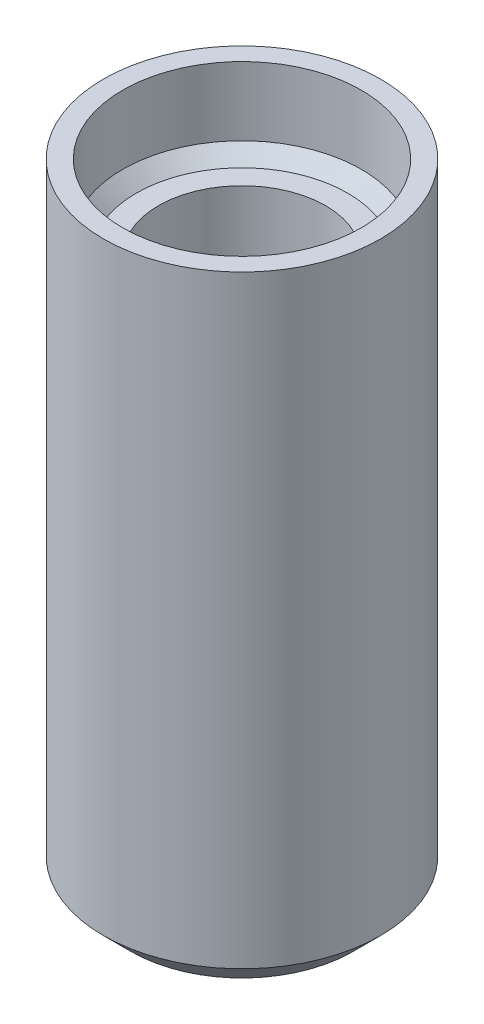
SolidWorks part; units mm, degrees
ref_plane "Front Plane" through (0, 0, 0) normal (0, 0, 1) x (1, 0, 0)
ref_plane "Top Plane" through (0, 0, 0) normal (0, 1, 0) x (1, 0, 0)
ref_plane "Right Plane" through (0, 0, 0) normal (1, 0, 0) x (0, 0, -1)
sketch "Sketch1" plane through (0, 0, 0) normal (0, 1, 0) x (1, 0, 0)
  line L0 (-2.5652, -1.65) -> (2.5652, -1.65)
  circle A0 centre (0, 0) radius 3.05
  circle A1 centre (0, 0) radius 5.05
  dimension "D1" = 6.1
  dimension "D3" = 1.65
  dimension "D2" = 2
extrude "Boss-Extrude1" add sketch "Sketch1" along normal blind 20 contours A1 A0 | L0 A0 region at (0, 0, 2.2227) region at (-4.9072, 0, 0)
sketch "Sketch2" plane through (0, 0, 0) normal (0, -1, 0) x (1, 0, 0)
  circle A1 centre (0, 0) radius 5.05
  circle A2 centre (0, 0) radius 5.05
  dimension "D1" = 0
extrude "Boss-Extrude2" add sketch "Sketch2" against normal blind 2
sketch "Sketch4" plane through (0, 20, 0) normal (0, 1, 0) x (1, 0, 0)
  circle A0 centre (0, 0) radius 4.35
  circle A1 centre (0, 0) radius 5.05
  circle A2 centre (0, 0) radius 5.05
  dimension "D1" = 0
  dimension "D2" = 0.7
extrude "Boss-Extrude3" add sketch "Sketch4" along normal blind 3
chamfer "Chamfer1" distance 1 angle 45 1 edges at (0, 0, 5.05)
chamfer "Chamfer2" distance 0.5 angle 45 1 edges at (0, 20, 4.35)
sketch "Sketch5" plane through (0, 0, 0) normal (0, -1, 0) x (1, 0, 0)
  line L0 (-1.326, 0) -> (1.326, 0) construction
  line L1 (-3.5217, -2) -> (3.5217, -2) construction
  circle A0 centre (0, 0) radius 4.05 construction
  text T0 "<b>1</b>" font "Calibri" height in points 16
  dimension "D1" = 2
extrude "Cut-Extrude1" cut sketch "Sketch5" against normal blind 0.4
extrude "Boss-Extrude4" add sketch "Sketch5<2>" against normal blind 0.4 separate body
sketch "Sketch5<2>" plane through (0, 0, 0) normal (0, -1, 0) x (1, 0, 0) same geometry as "Sketch5"
equation "\"ID\"= 6.3"
equation "\"notch\"= 6.3 / 2 - 1.5"
equation "\"D3@Sketch1\"=\"notch\""
